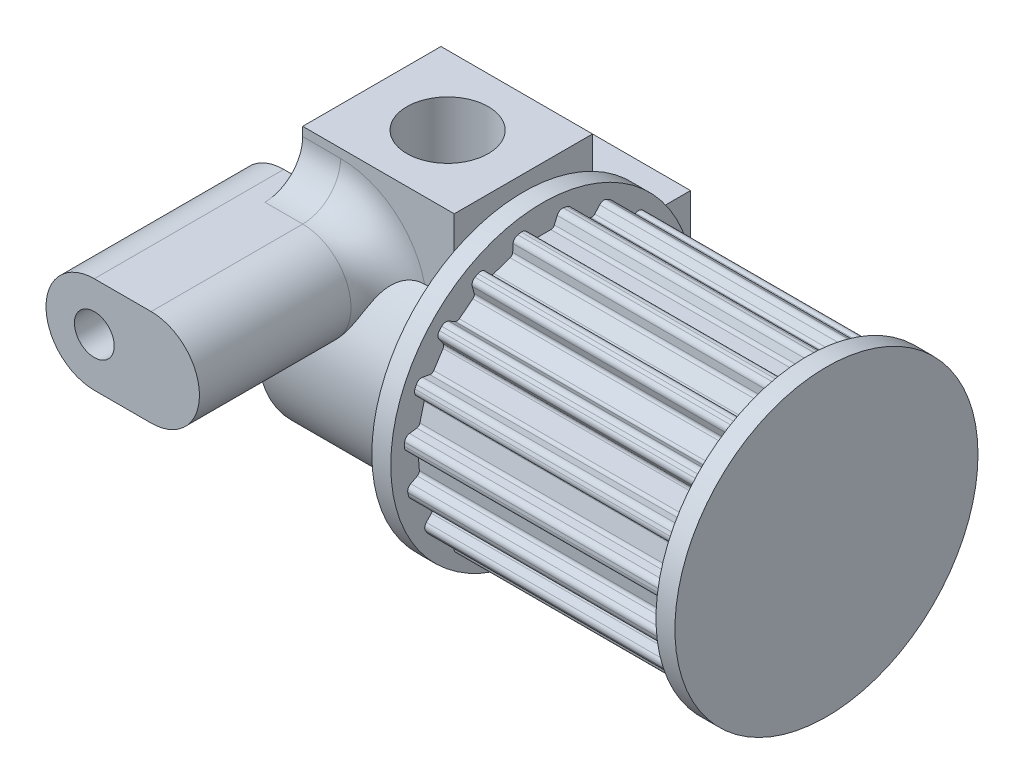
SolidWorks part; units mm, degrees
material "PLA Black"
ref_plane "Front" through (0, 0, 0) normal (0, 0, 1) x (1, 0, 0)
ref_plane "Top" through (0, 0, 0) normal (0, 1, 0) x (1, 0, 0)
ref_plane "Right" through (0, 0, 0) normal (1, 0, 0) x (0, 0, -1)
sketch "Sketch1" plane through (0, 0, 0) normal (1, 0, 0) x (0, 0, -1)
  line L0 (1.118, 1) -> (-1.118, 1) construction
  line L1 (-3.65, 4.8249) -> (3.65, 4.8249)
  line L2 (4.8249, 3.65) -> (4.8249, -3.65)
  line L3 (0, 0) -> (11.6334, 0) construction
  line L4 (0, 0) -> (0, 8.6732) construction
  arc A0 (-1.118, 1) -> (1.118, 1) centre (0, 0) ccw construction
  circle A1 centre (0, 0) radius 1.75
  arc A2 (4.8249, -3.65) -> (-3.65, 4.8249) centre (0, 0) cw
  arc A3 (4.8249, 3.65) -> (3.65, 4.8249) centre (0, 0) ccw
  dimension "D1" = 3
  dimension "D3" = 0.25
  dimension "D5" = 6.05
  dimension "D2" = 1
  dimension "D4" = 7.3
extrude "Boss-Extrude1" add sketch "Sketch1" along normal mid plane 8
sketch "Sketch2" plane through (0, 4.8249, 0) normal (0, 1, 0) x (1, 0, 0)
  circle A0 centre (0, 0) radius 2.15
  dimension "D1" = 4.3
extrude "Cut-Extrude1" cut sketch "Sketch2" against normal blind 5
sketch "Sketch7" plane through (4, 0, 0) normal (1, 0, 0) x (0, 0, -1)
  circle A0 centre (0, 0) radius 1.75 construction
  circle A1 centre (0, 0) radius 7.3
  circle A2 centre (0, 0) radius 1.75
  dimension "D1" = 14.6
extrude "Boss-Extrude5" add sketch "Sketch7" along normal blind 15
sketch "Sketch8" plane through (19, 0, 0) normal (1, 0, 0) x (0, 0, -1)
  line L0 (-0.4541, 6.5499) -> (0.4528, 6.5499)
  line L1 (0.6374, 6.6734) -> (0.7865, 7.0333)
  line L2 (-0.6389, 6.6734) -> (-0.788, 7.0333)
  line L6 (0, 9.2013) -> (0, 0) construction
  arc A0 (0.4528, 6.5499) -> (0.6374, 6.6734) centre (0.4526, 6.7499) ccw
  arc A1 (-0.4541, 6.5499) -> (-0.6389, 6.6734) centre (-0.4541, 6.7499) cw
  arc A2 (0.7865, 7.0333) -> (1.1093, 7.2152) centre (1.0638, 6.9187) cw
  arc A3 (-0.788, 7.0333) -> (-1.1108, 7.215) centre (-1.0652, 6.9185) ccw
  circle A4 centre (0, 0) radius 7.3 construction
  arc A5 (-1.1108, 7.215) -> (1.1093, 7.2152) centre (0, 0) cw
  point P3 (-0.0007, 6.5499)
  point P15 (0, 9.84)
extrude "Cut-Extrude3" cut sketch "Sketch8" against normal up to surface (15 mm away) up to face at (4, 0, -7.3)
pattern_circular "CirPattern1" count 19 over 360 about axis through (19, 0, 0) along (-1, 0, 0) of "Cut-Extrude3"
sketch "Sketch9" plane through (19, 0, 0) normal (1, 0, 0) x (0, 0, -1)
  circle A0 centre (0, 0) radius 8
  dimension "D1" = 16
extrude "Boss-Extrude6" add sketch "Sketch9" along normal blind 1
sketch "Sketch10" plane through (4, 0, 0) normal (-1, 0, 0) x (0, 0, 1)
  circle A0 centre (0, 0) radius 8
  circle A1 centre (0, 0) radius 8 construction
extrude "Boss-Extrude7" add sketch "Sketch10" against normal blind 1
sketch "Sketch3" plane through (0, 0, -4.8249) normal (0, 0, -1) x (-1, 0, 0)
  circle A0 centre (0, 0) radius 2.15
  dimension "D1" = 4.3
extrude "Cut-Extrude2" cut sketch "Sketch3" against normal blind 5
sketch "Sketch4" plane through (0, 4.8249, 0) normal (0, 1, 0) x (1, 0, 0)
  line L0 (4, 3.65) -> (-4, 3.65) construction
  line L2 (4, -3.65) -> (-4, -3.65) construction
  line L3 (-4, 3.65) -> (-4, -3.65) construction
  line L4 (4, 3.65) -> (-4, 3.65)
  line L5 (4, 3.65) -> (4, -3.65)
  line L6 (4, -3.65) -> (-4, -3.65)
  line L7 (-4, 3.65) -> (-4, -3.65)
  line L8 (4, 7.3) -> (4, -7.3) construction
  circle A0 centre (0, 0) radius 2.15 construction
  circle A1 centre (0, 0) radius 2.15
extrude "Boss-Extrude2" add sketch "Sketch4" along normal blind 4
sketch "Sketch5" plane through (0, 0, -4.8249) normal (0, 0, -1) x (-1, 0, 0)
  line L0 (-4, 3.65) -> (4, 3.65) construction
  line L1 (4, -3.65) -> (4, 3.65) construction
  line L2 (-4, -3.65) -> (4, -3.65) construction
  line L4 (-4, 3.65) -> (4, 3.65)
  line L5 (4, -3.65) -> (4, 3.65)
  line L6 (-4, -3.65) -> (4, -3.65)
  line L7 (-4, -3.65) -> (-4, 3.65)
  line L8 (-4, -7.3) -> (-4, 7.3) construction
  circle A0 centre (0, 0) radius 2.15 construction
  circle A1 centre (0, 0) radius 2.15
extrude "Boss-Extrude3" add sketch "Sketch5" along normal blind 4
ref_axis "Axis1" through (4, 0, 0) along (-1, 0, 0)
sketch "Sketch6" plane through (0, 0, 3.65) normal (0, 0, 1) x (1, 0, 0)
  line L0 (-4, 8.8249) -> (-4, 4.8249) construction
  line L2 (-2, 6.3555) -> (-5, 6.3555)
  line L3 (-5, 1.2545) -> (-2, 1.2545)
  line L6 (4, 0) -> (-4, 0) construction
  circle A0 centre (-5, 3.805) radius 1.0505
  arc A1 (-5, 6.3555) -> (-5, 1.2545) centre (-5, 3.805) ccw
  arc A2 (-2, 6.3555) -> (-2, 1.2545) centre (-2, 3.805) cw
  dimension "D1" = 2.101
  dimension "D2" = 3.805
  dimension "D3" = 1.5
  dimension "D4" = 1
  dimension "D5" = 3
extrude "Boss-Extrude4" add sketch "Sketch6" along normal blind 10
fillet "Fillet1" radius 2 2 edges at (-0.6029, 5.9388, 3.65) (-3, 6.3555, 3.65)
equation "\"knee_angle\"= 70"
equation "\"ankle_angle\" = 80"
equation "\"hip_angle\" = 40"
equation "\"spring_ankle_parallel_arm_diameter\"= 1.1"
equation "\"spring_ankle_parallel_arm_length\"= 13"
equation "\"spring_ankle_parallel_intern_diameter\"= 5.7"
equation "\"spring_ankle_parallel_angle\"= \"ankle_angle\""
equation "\"spring_ankle_parallel_turns\"= 3"
equation "\"spring_ankle_parallel_pitch\"= \"spring_ankle_parallel_arm_diameter\" * 1.01"
equation "\"spring_ankle_parallel_cutting_distance\"= (1-\"spring_ankle_parallel_angle\" / 360) * \"spring_ankle_parallel_pitch\""
equation "\"spring_ankle_serial_arm_diameter\"= 1.91"
equation "\"spring_ankle_serial_arm_length\"= 10"
equation "\"spring_ankle_serial_intern_diameter\"= 5.7"
equation "\"spring_ankle_serial_angle\"= \"90\""
equation "\"spring_ankle_serial_turns\"= 3"
equation "\"spring_ankle_serial_pitch\"= \"spring_ankle_serial_arm_diameter\" * 1.01"
equation "\"spring_ankle_serial_cutting_distance\"= (1-\"spring_ankle_serial_angle\" / 360) * \"spring_ankle_serial_pitch\""
equation "\"spring_knee_parallel_arm_diameter\"= 1.1"
equation "\"spring_knee_parallel_arm_length\"= 13"
equation "\"spring_knee_parallel_intern_diameter\"= 5.7"
equation "\"spring_knee_parallel_angle\"= -\"knee_angle\" + 90"
equation "\"spring_knee_parallel_turns\"= 3"
equation "\"spring_knee_parallel_pitch\"= \"spring_knee_parallel_arm_diameter\" * 1.01"
equation "\"spring_knee_parallel_cutting_distance\"= (1-(\"spring_knee_parallel_angle\") / 360) * \"spring_knee_parallel_pitch\""
equation "\"spring_knee_serial_arm_diameter\"= 1.91"
equation "\"spring_knee_serial_arm_length\"= 10"
equation "\"spring_knee_serial_intern_diameter\"= 5.7"
equation "\"spring_knee_serial_angle\"= \"90\""
equation "\"spring_knee_serial_turns\"= 3"
equation "\"spring_knee_serial_pitch\"= \"spring_knee_serial_arm_diameter\" * 1.01"
equation "\"spring_knee_serial_cutting_distance\"= (1-\"spring_knee_serial_angle\" / 360) * \"spring_knee_serial_pitch\""
equation "\"D2@Sketch6\" = ( \"spring_knee_serial_intern_diameter\" + \"spring_knee_serial_arm_diameter\" ) / 2"
equation "\"D1@Sketch6\"=\"spring_knee_serial_arm_diameter\"*1.1"
